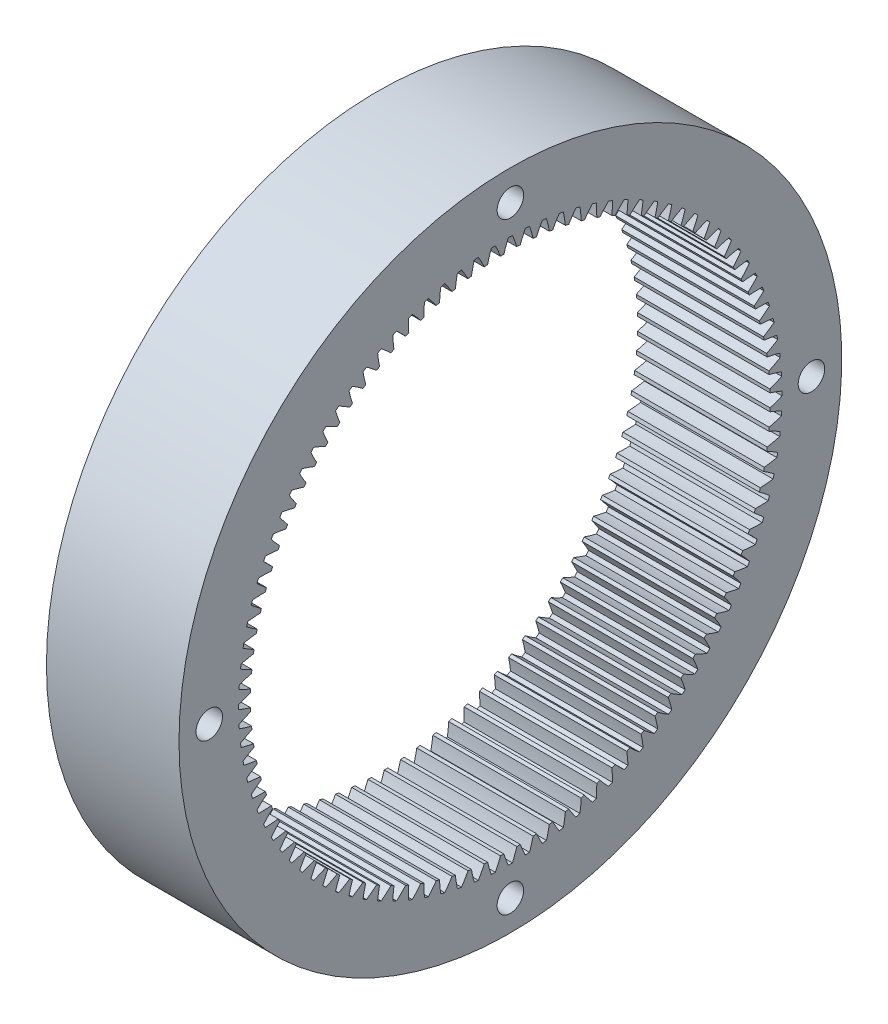
SolidWorks part; units mm, degrees
ref_plane "Plane1" through (0, 0, 0) normal (0, 0, 1) x (1, 0, 0)
ref_plane "Plane2" through (0, 0, 0) normal (0, 1, 0) x (1, 0, 0)
ref_plane "Plane3" through (0, 0, 0) normal (1, 0, 0) x (0, 0, -1)
other "Configuration Table"
sketch "HoldingSke" plane through (0, 0, 0) normal (0, 1, 0) x (1, 0, 0)
  line L0 (0, 0) -> (-0.4341, -2.462)
  line L1 (-15, 0) -> (100, 0) construction
  line L2 (0, 0) -> (-2.1039, 2.3779)
  line L3 (0, 0) -> (-11.863, 4.5341)
  line L4 (0, 0) -> (-1.4996, 8.5048)
  line L5 (0, 0) -> (-23.7986, -8.8762)
  line L6 (0, 0) -> (-10.5278, -7.1032)
  line L7 (-2.1039, 2.3779) -> (3.3635, 27.1825)
  line L8 (-76.2, 2.7779) -> (-54.61, 2.7779)
  line L9 (-71.009, 38.7566) -> (-53.1078, 45.2721)
  line L10 (-76.2, 71.12) -> (104.1128, 71.12)
  line L11 (0, 0) -> (-10, 0)
  line L12 (-76.2, 101.6) -> (-76.185, 101.6)
  line L13 (24.9733, 27.94) -> (52.9518, 28.4284)
  line L14 (24.9733, 27.94) -> (24.9743, 27.94)
  line L15 (24.9733, 27.94) -> (100.4006, 29.5858)
  circle A0 centre (0, 0) radius 25
  circle A1 centre (0, 0) radius 12.7
  circle A2 centre (0, 0) radius 12.7
  dimension "Num_teeth" = 100
  dimension "Pitch_radius" = 180.3128
  dimension "Width" = 10
  dimension "Diameter" = 50
sketch "BasProSke" plane through (0, 0, 0) normal (0, 1, 0) x (1, 0, 0)
  line L0 (-10, 0) -> (60, 0) construction
  line L1 (0, 19.6) -> (0, 25)
  line L2 (0, 19.6) -> (10, 19.6)
  line L3 (10, 19.6) -> (10, 25)
  line L4 (10, 25) -> (0, 25)
  dimension "Thickness" = 10
  dimension "Diameter" = 50
revolve "Base-Revolve" add sketch "BasProSke" angle 360 about L0
sketch "TooCutSke" plane through (0, 0, 0) normal (1, 0, 0) x (0, 0, -1)
  line L3 (0.3516, 19.9969) -> (0.3516, 53.6633) construction
  line L4 (0, 0) -> (0, 59.563) construction
  line L5 (0, 0) -> (-2.1462, 68.2938) construction
  line L6 (-9.0673, 16.6379) -> (37.2928, 18.0948) construction
  circle A0 centre (0, 0) radius 20 construction
  circle A1 centre (0, 0) radius 20.501 construction
  circle A2 centre (0, 0) radius 16.9145 construction
  circle A3 centre (0, 0) radius 19.5746 construction
  arc A4 (0.4937, 19.5684) -> (0.1566, 20.5004) centre (-9.0673, 16.6379) ccw
  arc A5 (0.4937, 19.5684) -> (-0.4937, 19.5684) centre (0, 0) ccw
  arc A6 (0.1566, 20.5004) -> (-0.1566, 20.5004) centre (0, 0) ccw
  arc A7 (-0.1566, 20.5004) -> (-0.4937, 19.5684) centre (9.0673, 16.6379) ccw
extrude "ToothCut" cut sketch "TooCutSke" along normal through all
fillet "Breaks" [suppressed] radius 0.04
fillet "RootFillets" [suppressed] radius 0.101
pattern_circular "TeethCuts" count 100 every 3.6 about axis through (-10, 0, 0) along (1, 0, 0) of "RootFillets", "Breaks", "ToothCut"
sketch "Sketch1" plane through (10, 0, 0) normal (1, 0, 0) x (0, 0, -1)
  circle A0 centre (0, 0) radius 22.715
  circle A1 centre (0, 22.715) radius 1
  circle A2 centre (22.715, 0) radius 1
  circle A3 centre (0, -22.715) radius 1
  circle A4 centre (-22.715, 0) radius 1
  dimension "D1" = 45.43
  dimension "D2" = 2
  dimension "D3" = 2
  dimension "D4" = 2
  dimension "D5" = 2
extrude "Cut-Extrude1" cut sketch "Sketch1" against normal through all contours A4 | A1 | A2 | A3
equation "' \"Module@HoldingSke\" = 6.35"
equation "' \"Num_teeth@HoldingSke\" = 24"
equation "' \"Ap@HoldingSke\" =  14.5"
equation "' \"Ap@HoldingSke\" = 14.5"
equation "' \"Width@HoldingSke\" = 12"
equation "' \"Diameter@HoldingSke\" = 8 * 25.4"
equation "' \"Show_teeth@HoldingSke\" = 100"
equation "' \"Backlash@HoldingSke\" = 0.009 * 25.4"
equation "' \"Addendum_fac@HoldingSke\" = 1.0"
equation "' \"Dedendum_fac@HoldingSke\" = 1.25"
equation "' \"Dedendum_add@HoldingSke\" = 0.00005 * 25.4"
equation "' \"Clearance_fac@HoldingSke\" = 0.25"
equation "\"Pitch@HoldingSke\" = 1 / \"Module@HoldingSke\" "
equation "\"Overcut_dia@TooCutSke\" = (\"Num_teeth@HoldingSke\" - 2 * \"Addendum_fac@HoldingSke\") / \"Pitch@HoldingSke\" - 0.002 * 25.4"
equation "\"Pitch_dia@TooCutSke\" = \"Num_teeth@HoldingSke\" / \"Pitch@HoldingSke\""
equation "\"Base_dia@TooCutSke\" = \"Num_teeth@HoldingSke\" / \"Pitch@HoldingSke\" * cos((\"Ap@HoldingSke\"  * 3.14159265 / 180)) * 0.90"
equation "\"Root_dia@TooCutSke\" = \"Num_teeth@HoldingSke\"  / \"Pitch@HoldingSke\" + 2 *  \"Dedendum_fac@HoldingSke\"/ \"Pitch@HoldingSke\" + \"Dedendum_add@HoldingSke\" * 2"
equation "\"Half_ang@TooCutSke\" = 180 / \"Num_teeth@HoldingSke\""
equation "\"Half_CT@TooCutSke\" = \"Num_teeth@HoldingSke\" / \"Pitch@HoldingSke\" * sin((3.14159265 / 2 / \"Num_teeth@HoldingSke\")) / 2 + 10 * \"Backlash@HoldingSke\" / 4"
equation "\"Flank_rad@TooCutSke\" = \"Num_teeth@HoldingSke\" / \"Pitch@HoldingSke\" / 4"
equation "\"Radius@RootFillets\"= \"Clearance_fac@HoldingSke\" / \"Pitch@HoldingSke\" + \"Dedendum_add@HoldingSke\""
equation "\"Break_rad@Breaks\" = 0.02 / \"Pitch@HoldingSke\" * 5"
equation "\"Num_teeth@TeethCuts\" = int( \"Show_teeth@HoldingSke\" ) + 1"
equation "\"Num_teeth@TeethCuts\" = ((sgn( \"Num_teeth@TeethCuts\" - \"Num_teeth@HoldingSke\" )-1)*( \"Num_teeth@TeethCuts\" - \"Num_teeth@HoldingSke\" ))/-2+ \"Num_teeth@HoldingSke\""
equation "\"Num_teeth@TeethCuts\" = ((sgn( \"Num_teeth@TeethCuts\" - 2.0)+1)*( \"Num_teeth@TeethCuts\" - 2.0))/2 +2.0"
equation "\"Angle@TeethCuts\" = 360.0 / \"Num_teeth@HoldingSke\""
equation "\"Diameter@BasProSke\" = \"Num_teeth@HoldingSke\"  / \"Pitch@HoldingSke\" + 2 *  \"Dedendum_fac@HoldingSke\"/ \"Pitch@HoldingSke\" + \"Dedendum_add@HoldingSke\" * 2 + 0.002 * 25.4"
equation "\"Diameter@BasProSke\" = ((sgn( \"Diameter@BasProSke\"  - \"Diameter@HoldingSke\" )+1)*( \"Diameter@BasProSke\"  - \"Diameter@HoldingSke\" ))/2 + \"Diameter@HoldingSke\""
equation "\"Inside_diameter@BasProSke\" =  (\"Num_teeth@HoldingSke\" - 2 * \"Addendum_fac@HoldingSke\") / \"Pitch@HoldingSke\" "
equation "\"Thickness@BasProSke\"  = \"Width@HoldingSke\""
